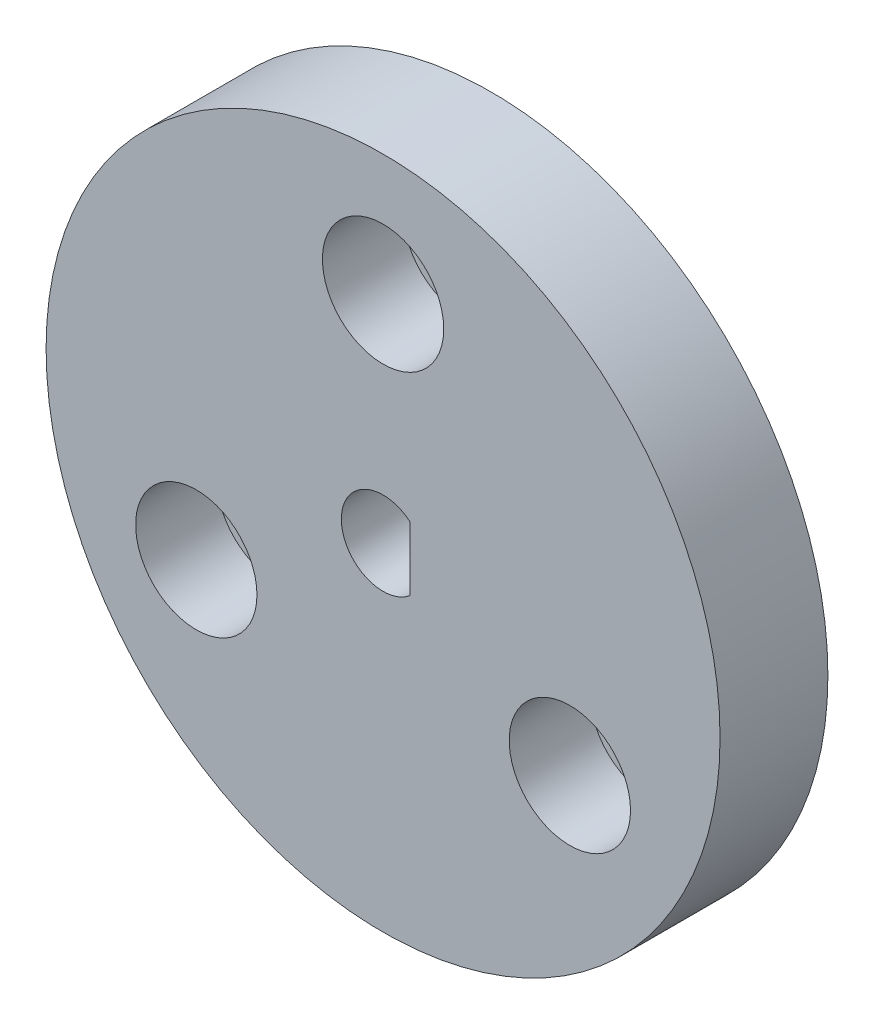
SolidWorks part; units mm, degrees
ref_plane "前视基准面" through (0, 0, 0) normal (0, 0, 1) x (1, 0, 0)
ref_plane "上视基准面" through (0, 0, 0) normal (0, 1, 0) x (1, 0, 0)
ref_plane "右视基准面" through (0, 0, 0) normal (1, 0, 0) x (0, 0, -1)
other "Configuration Table"
sketch "草图1" plane through (0, 0, 0) normal (0, 0, 1) x (1, 0, 0)
  line L0 (0, 0) -> (1.6914, 0.6156) construction
  line L1 (0, 0) -> (1.5832, 0.5954)
  line L2 (0, 0) -> (1.5832, -0.5954)
  line L3 (0, 0) -> (1.6914, -0.6156) construction
  line L4 (0, 0) -> (2.55, 0) construction
  line L5 (1.6914, 0.6156) -> (1.6914, -0.6156) construction
  circle A0 centre (0, 0) radius 1.65
  circle A1 centre (0, 0) radius 2.55
  circle A2 centre (0, 0) radius 1.6914 construction
  circle A3 centre (0, 0) radius 1.8 construction
  circle A4 centre (0, 0) radius 3
  spline S0 degree 4 poles (1.5832, 0.5954) (1.5953, 0.5999) (1.6299, 0.61) (1.6985, 0.6188) (1.8107, 0.6176) (1.9542, 0.5935) (2.1323, 0.5368) (2.3288, 0.4397) (2.527, 0.3033) (2.7182, 0.1281) (2.8863, -0.0692) (3.0309, -0.2841) (3.1583, -0.5243) (3.284, -0.8365) (3.3855, -1.2255) (3.4358, -1.6902) (3.4119, -2.2085) (3.3126, -2.7182) (3.1474, -3.2089) (2.918, -3.6756) (2.6387, -4.1089) (2.3029, -4.5102) (1.9385, -4.866) (1.5141, -5.1906) (1.1742, -5.4065) (0.7714, -5.6132) (0.5343, -5.7151) (0.2601, -5.8236) (0.1183, -5.8645) (-0.005, -5.9055) (-0.0434, -5.9147) (-0.0704, -5.9226) (-0.0848, -5.927) knots 0 0 0 0 0 0.005604 0.015718 0.02996 0.048734 0.068727 0.096889 0.125051 0.153212 0.181374 0.209535 0.237696 0.271429 0.327752 0.384075 0.440398 0.496721 0.553044 0.609367 0.66569 0.722013 0.778336 0.834659 0.890982 0.909091 0.954545 0.977273 0.988636 0.994318 1 1 1 1 1 construction
  spline S1 degree 4 poles (1.5832, 0.5954) (1.5953, 0.5999) (1.6299, 0.61) (1.6985, 0.6188) (1.8107, 0.6176) (1.9542, 0.5935) (2.1323, 0.5368) (2.3288, 0.4397) (2.527, 0.3033) (2.7182, 0.1281) (2.8863, -0.0692) (3.0309, -0.2841) (3.1583, -0.5243) (3.284, -0.8365) (3.3855, -1.2255) (3.4358, -1.6902) (3.4119, -2.2085) (3.3126, -2.7182) (3.1474, -3.2089) (2.918, -3.6756) (2.6387, -4.1089) (2.3029, -4.5102) (1.9385, -4.866) (1.5141, -5.1906) (1.1742, -5.4065) (0.8753, -5.5599) (0.734, -5.626) (0.6996, -5.6416) knots 0 0 0 0 0 0.005604 0.015718 0.02996 0.048734 0.068727 0.096889 0.125051 0.153212 0.181374 0.209535 0.237696 0.271429 0.327752 0.384075 0.440398 0.496721 0.553044 0.609367 0.66569 0.722013 0.778336 0.834659 0.890982 0.909091 0.909091 0.909091 0.909091 0.909091
  spline S2 degree 4 poles (1.5832, -0.5954) (1.5953, -0.5999) (1.6299, -0.61) (1.6985, -0.6188) (1.8107, -0.6176) (1.9542, -0.5935) (2.1323, -0.5368) (2.3288, -0.4397) (2.527, -0.3033) (2.7182, -0.1281) (2.8863, 0.0692) (3.0309, 0.2841) (3.1583, 0.5243) (3.284, 0.8365) (3.3855, 1.2255) (3.4358, 1.6902) (3.4119, 2.2085) (3.3126, 2.7182) (3.1474, 3.2089) (2.918, 3.6756) (2.6387, 4.1089) (2.3029, 4.5102) (1.9385, 4.866) (1.5141, 5.1906) (1.1742, 5.4065) (0.7714, 5.6132) (0.5343, 5.7151) (0.2601, 5.8236) (0.1183, 5.8645) (-0.005, 5.9055) (-0.0434, 5.9147) (-0.0704, 5.9226) (-0.0848, 5.927) knots 0 0 0 0 0 0.005604 0.015718 0.02996 0.048734 0.068727 0.096889 0.125051 0.153212 0.181374 0.209535 0.237696 0.271429 0.327752 0.384075 0.440398 0.496721 0.553044 0.609367 0.66569 0.722013 0.778336 0.834659 0.890982 0.909091 0.954545 0.977273 0.988636 0.994318 1 1 1 1 1 construction
  spline S3 degree 4 poles (1.5832, -0.5954) (1.5953, -0.5999) (1.6299, -0.61) (1.6985, -0.6188) (1.8107, -0.6176) (1.9542, -0.5935) (2.1323, -0.5368) (2.3288, -0.4397) (2.527, -0.3033) (2.7182, -0.1281) (2.8863, 0.0692) (3.0309, 0.2841) (3.1583, 0.5243) (3.284, 0.8365) (3.3855, 1.2255) (3.4358, 1.6902) (3.4119, 2.2085) (3.3126, 2.7182) (3.1474, 3.2089) (2.918, 3.6756) (2.6387, 4.1089) (2.3029, 4.5102) (1.9385, 4.866) (1.5141, 5.1906) (1.1742, 5.4065) (0.8753, 5.5599) (0.734, 5.626) (0.6996, 5.6416) knots 0 0 0 0 0 0.005604 0.015718 0.02996 0.048734 0.068727 0.096889 0.125051 0.153212 0.181374 0.209535 0.237696 0.271429 0.327752 0.384075 0.440398 0.496721 0.553044 0.609367 0.66569 0.722013 0.778336 0.834659 0.890982 0.909091 0.909091 0.909091 0.909091 0.909091
  point P16 (1.6914, 0)
  dimension "内啮合齿顶圆直径" = 3.3
  dimension "内啮合分度圆直径" = 3.6
  dimension "内啮合基圆直径" = 3.3829
  dimension "内啮合齿根圆直径" = 5.1
  dimension "外径" = 6
  dimension "渐开线镜像线夹角" = 20
extrude "凸台-拉伸1" add sketch "草图1" along normal blind 4 contours A4 | A0
extrude "切除-拉伸2" cut sketch "草图1<3>" along normal through all contours A0 S3 A1 S1 region at (2.0287, 0, 0)
sketch "草图1<3>" plane through (0, 0, 0) normal (0, 0, 1) x (1, 0, 0) same geometry as "草图1"
pattern_circular "阵列(圆周)1" count 9 over 360 about axis through (0, 0, 4) along (0, 0, 1) of "切除-拉伸2"
sketch "草图2" plane through (0, 0, 0) normal (0, 0, -1) x (-1, 0, 0)
  circle A0 centre (0, 0) radius 3
  circle A1 centre (0, 0) radius 3 construction
  circle A2 centre (0, 0) radius 5
  dimension "D1" = 10
extrude "凸台-拉伸2" add sketch "草图2" against normal up to surface (4 mm away) contours A2 up to face at (3, 0, 4)
sketch "草图3" plane through (0, 0, 0) normal (0, 0, 1) x (1, 0, 0)
  circle A0 centre (0, 8) radius 2.25
  circle A1 centre (0, 8) radius 1.5
  circle A2 centre (0, 0) radius 12.5
  circle A3 centre (6.9282, -4) radius 1.5
  circle A4 centre (6.9282, -4) radius 2.25
  circle A5 centre (-6.9282, -4) radius 1.5
  circle A6 centre (-6.9282, -4) radius 2.25
  circle A7 centre (0, 0) radius 5
  circle A10 centre (0, 0) radius 5 construction
  point P14 (0, 0)
  dimension "D4" = 3
  dimension "D5" = 4.5
  dimension "D1" = 25
  dimension "D2" = 3
  dimension "D3" = 8
extrude "凸台-拉伸4" add sketch "草图3" along normal blind 4 contours A2 | A5 | A3 | A1 | A7
extrude "切除-拉伸3" cut sketch "草图3<3>" against normal offset from surface (3 mm away) 1 from surface contours A0 | A4 | A6 up to face at (12.5, 0, 0) starting at face at (1.5, 8, 4)
sketch "草图3<3>" plane through (0, 0, 0) normal (0, 0, 1) x (1, 0, 0) same geometry as "草图3"
sketch "草图4" plane through (0, 0, 4) normal (0, 0, 1) x (1, 0, 0)
  line L0 (1, -1.1843) -> (1, 1.1843)
  circle A0 centre (0, 0) radius 1.55
  dimension "D1" = 3.1
  dimension "D2" = 1
extrude "切除-拉伸4" cut sketch "草图4" against normal through all contours L0 A0 region at (-0.1667, 0, 4)
equation "\"m\"= 0.4'模数"
equation "\"z1\"= 9'外啮合齿轮数"
equation "\"a\"= 20度'压力角"
equation "\"z2\"= 9'内啮合齿轮数"
equation "\"hax\"= 1'齿顶高系数"
equation "\"cx\"= 0.25'顶隙系数"
equation "\"ha\"= \"hax\" * \"m\"'齿顶高"
equation "\"hf\"= ( \"hax\" + \"cx\" ) * \"m\"'齿根高"
equation "\"d1\"= \"m\" * \"z1\"'外啮合分度圆直径"
equation "\"da1\"= ( \"z1\" + 2 ) * \"m\"'外啮合齿顶圆直径"
equation "\"df1\"= \"d1\" - 2 * \"hf\"'外啮合齿根圆直径"
equation "\"db1\"= \"d1\" * cos ( \"a\" )'外啮合基圆直径"
equation "\"p\"= \"m\" * PI'齿距"
equation "\"d2\"= \"m\" * \"z2\"'内啮合分度圆直径"
equation "\"db2\"= \"d2\" * cos ( \"a\" )'内啮合基圆直径"
equation "\"da2\"= ( \"z2\" - 2 ) * \"m\"'内啮合齿顶圆直径"
equation "\"df2\"= \"d2\" + 2 * \"hf\"'内啮合齿根圆直径"
equation "\"内啮合齿顶圆直径@草图1\" = \"da2\" + 1 * \"hf\""
equation "\"内啮合齿根圆直径@草图1\" = \"df2\" + 1 * \"hf\""
equation "\"内啮合分度圆直径@草图1\"= \"d2\""
equation "\"内啮合基圆直径@草图1\"= \"db2\""
equation "\"渐开线镜像线夹角@草图1\"= 360度 / 4 / \"z2\" + 360度 / 4 / \"z2\""
equation "\"do\"= IIF ( \"edo\" >= ( \"df2\" + 1 ) , \"edo\" , ( \"df2\" + 1 ) )'外圈直径"
equation "\"h\"= 4'厚度"
equation "\"外径@草图1\"= \"do\""
equation "\"厚度@凸台-拉伸1\"= \"h\""
equation "\"内啮合齿轮数@阵列(圆周)1\"= \"z2\""
equation "\"edo\"= 6'期望的外圈直径"
